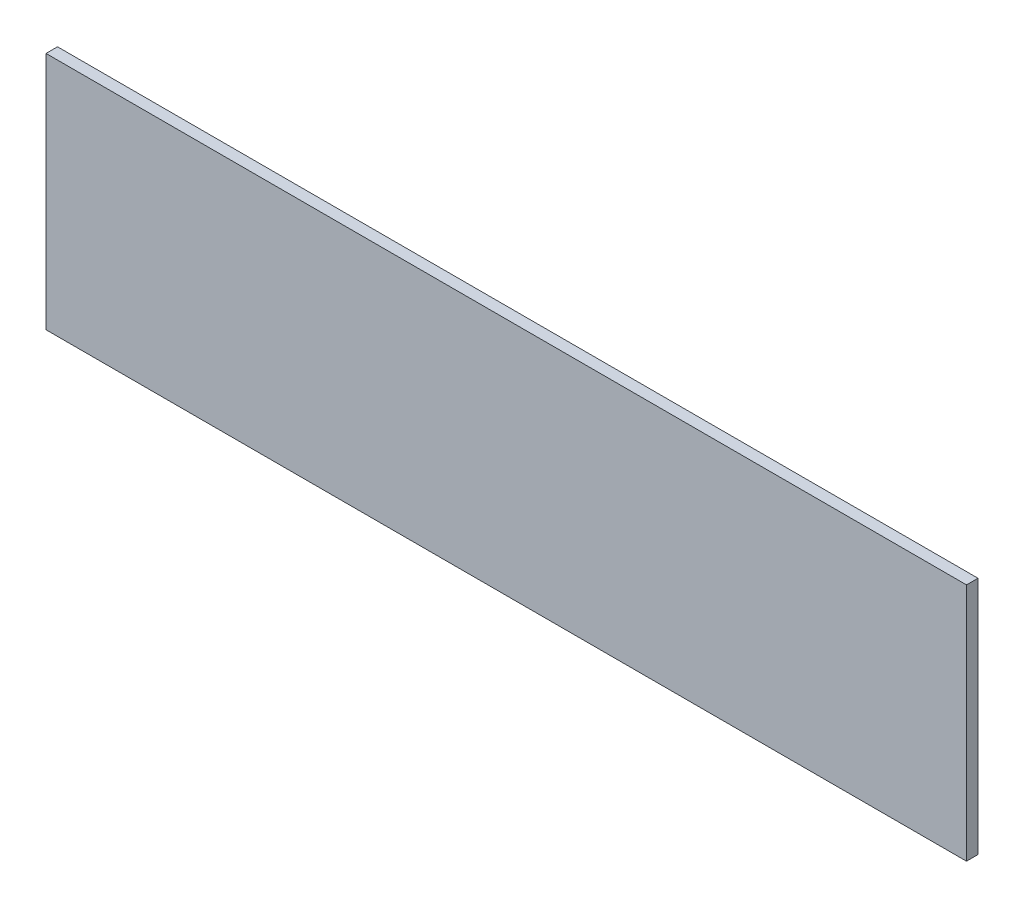
SolidWorks part; units mm, degrees
ref_plane "Front Plane" through (0, 0, 0) normal (0, 0, 1) x (1, 0, 0)
ref_plane "Top Plane" through (0, 0, 0) normal (0, 1, 0) x (1, 0, 0)
ref_plane "Right Plane" through (0, 0, 0) normal (1, 0, 0) x (0, 0, -1)
sketch "Sketch2" plane through (0, 0, 0) normal (0, 0, 1) x (1, 0, 0)
  line L1 (0, 0) -> (-254, 0)
  line L2 (0, 0) -> (0, 66.04)
  line L3 (0, 66.04) -> (-254, 66.04)
  line L4 (-254, 0) -> (-254, 66.04)
  dimension "D1" = 66.04
  dimension "D2" = 254
extrude "Boss-Extrude1" add sketch "Sketch2" along normal blind 3.175
